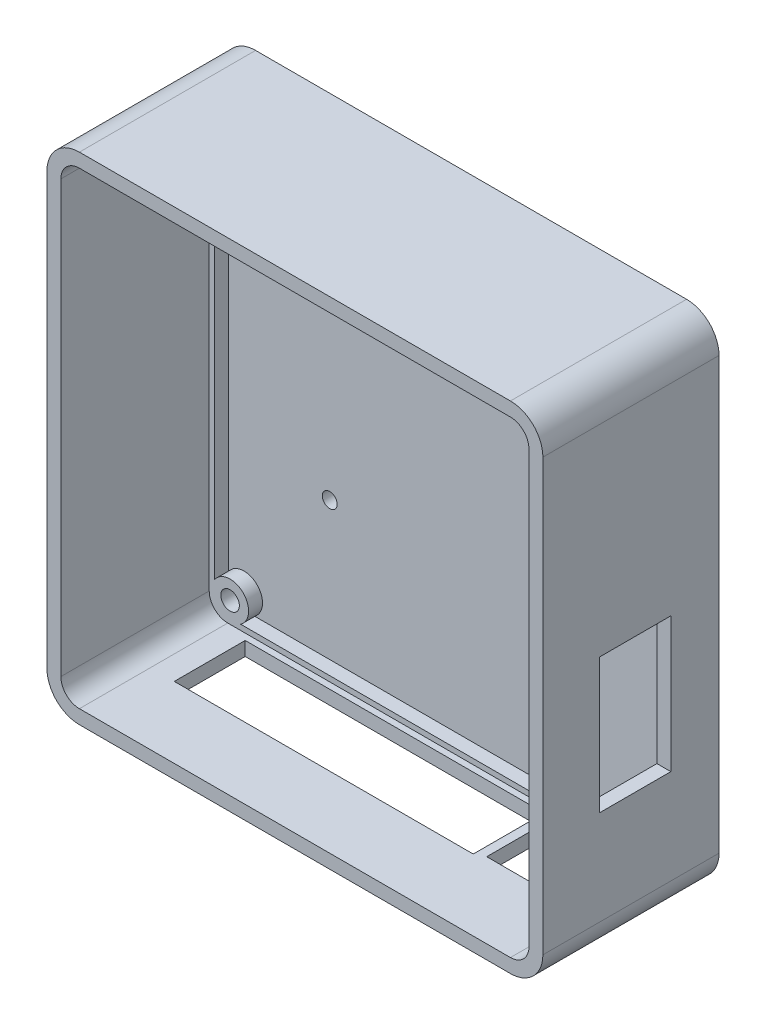
SolidWorks part; units mm, degrees
ref_plane "Piano frontale" through (0, 0, 0) normal (0, 0, 1) x (1, 0, 0)
ref_plane "Piano superiore" through (0, 0, 0) normal (0, 1, 0) x (1, 0, 0)
ref_plane "Piano destro" through (0, 0, 0) normal (1, 0, 0) x (0, 0, -1)
sketch "Schizzo1" plane through (0, 0, 94.0033) normal (0, 0, -1) x (-1, 0, 0)
  line L0 (-18.8461, 51.2441) -> (-18.8461, -40.7561) construction
  line L1 (-19.3461, 55.7314) -> (81.6287, 55.7314)
  line L2 (-19.3461, 55.7314) -> (-19.3461, -45.2434)
  line L3 (-19.3461, -45.2434) -> (81.6287, -45.2434)
  line L4 (81.6287, 55.7314) -> (81.6287, -45.2434)
  line L5 (81.1287, -40.7561) -> (81.1287, 51.2441) construction
  line L6 (77.1414, 55.2314) -> (-14.8588, 55.2314) construction
  line L7 (-14.8588, -44.7434) -> (77.1414, -44.7434) construction
  dimension "D1" = 0.5
  dimension "D2" = 0.5
  dimension "D3" = 0.5
  dimension "D4" = 0.5
extrude "Estrusione-Estrusione1" add sketch "Schizzo1" along normal blind 3
sketch "Schizzo3" plane through (0, 0, 94.0033) normal (0, 0, 1) x (1, 0, 0)
  line L0 (-81.6287, -45.2434) -> (-81.6287, 55.7314) construction
  line L1 (-81.6287, 55.7314) -> (19.3461, 55.7314) construction
  circle A0 centre (-77.1287, 51.2314) radius 2
  circle A1 centre (14.8713, 51.2314) radius 2
  circle A2 centre (-77.1287, -40.7686) radius 2
  circle A3 centre (14.8713, -40.7686) radius 2
  dimension "D5" = 4
  dimension "D6" = 4
  dimension "D7" = 4
  dimension "D8" = 4
  dimension "D1" = 4.5
  dimension "D2" = 4.5
  dimension "D3" = 92
  dimension "D4" = 92
extrude "Taglio-Estrusione1" cut sketch "Schizzo3" against normal blind 10
fillet "Raccordo1" radius 4 4 edges at (-81.6287, 55.7314, 92.5033) (-81.6287, -45.2434, 92.5033) (19.3461, -45.2434, 92.5033) (19.3461, 55.7314, 92.5033)
sketch "Schizzo4" plane through (0, 0, 94.0033) normal (0, 0, 1) x (1, 0, 0)
  line L7 (-74.8729, -44.0718) -> (12.6155, -44.0718)
  line L10 (18.1746, 48.9756) -> (18.1746, -38.5128)
  line L11 (-80.4571, 49.0129) -> (-80.4571, -38.5502)
  line L12 (-74.9102, 54.5598) -> (12.6529, 54.5598)
  arc A2 (-74.8729, -44.0718) -> (-80.4571, -38.5502) centre (-77.1287, -40.7686) ccw
  arc A4 (12.6529, 54.5598) -> (18.1746, 48.9756) centre (14.8713, 51.2314) ccw
  arc A5 (-80.4571, 49.0129) -> (-74.9102, 54.5598) centre (-77.1287, 51.2314) ccw
  arc A6 (18.1746, -38.5128) -> (12.6155, -44.0718) centre (14.8713, -40.7686) ccw
  dimension "D1" = 8
  dimension "D2" = 8
  dimension "D4" = 8
extrude "Taglio-Estrusione2" cut sketch "Schizzo4" against normal blind 3
sketch "Schizzo5" plane through (0, 0, 94.0033) normal (0, 0, 1) x (1, 0, 0)
  line L0 (19.3461, 51.7314) -> (19.3461, -41.2434) construction
  line L1 (-77.6287, 58.7314) -> (15.3461, 58.7314)
  line L2 (-84.6287, 51.7314) -> (-84.6287, -41.2434)
  line L3 (-77.6287, -48.2434) -> (15.3461, -48.2434)
  line L4 (22.3461, 51.7314) -> (22.3461, -41.2434)
  line L5 (-77.6287, 55.7314) -> (15.3461, 55.7314)
  line L6 (-81.6287, 51.7314) -> (-81.6287, -41.2434)
  line L7 (-77.6287, -45.2434) -> (15.3461, -45.2434)
  line L8 (19.3461, 51.7314) -> (19.3461, -41.2434)
  line L9 (-81.6287, -41.2434) -> (-81.6287, 51.7314) construction
  line L10 (15.3461, -45.2434) -> (-77.6287, -45.2434) construction
  arc A0 (-81.6287, -41.2434) -> (-77.6287, -45.2434) centre (-77.6287, -41.2434) ccw
  arc A1 (-81.6287, 51.7314) -> (-77.6287, 55.7314) centre (-77.6287, 51.7314) cw
  arc A2 (19.3461, -41.2434) -> (15.3461, -45.2434) centre (15.3461, -41.2434) cw
  arc A3 (19.3461, 51.7314) -> (15.3461, 55.7314) centre (15.3461, 51.7314) ccw
  arc A4 (-77.6287, -48.2434) -> (-84.6287, -41.2434) centre (-77.6287, -41.2434) cw
  arc A5 (22.3461, -41.2434) -> (15.3461, -48.2434) centre (15.3461, -41.2434) cw
  arc A6 (15.3461, 58.7314) -> (22.3461, 51.7314) centre (15.3461, 51.7314) cw
  arc A7 (-84.6287, 51.7314) -> (-77.6287, 58.7314) centre (-77.6287, 51.7314) cw
  dimension "D1" = 4
  dimension "D2" = 4
  dimension "D10" = 4
  dimension "D11" = 4
  dimension "D12" = 7
  dimension "D13" = 7
  dimension "D14" = 7
  dimension "D15" = 7
  dimension "D3" = 0
  dimension "D4" = 0
  dimension "D5" = 3
  dimension "D6" = 3
  dimension "D7" = 3
  dimension "D8" = 0
  dimension "D9" = 3
extrude "Estrusione-Estrusione2" add sketch "Schizzo5" along normal blind 32 and the other way blind 3
sketch "Schizzo6" plane through (0, 0, 91.0033) normal (0, 0, -1) x (-1, 0, 0)
  line L1 (-15.3461, 58.7314) -> (77.6287, 58.7314)
  line L2 (-22.3461, 51.7314) -> (-22.3461, -41.2434)
  line L3 (-15.3461, -48.2434) -> (77.6287, -48.2434)
  line L4 (84.6287, 51.7314) -> (84.6287, -41.2434)
  arc A0 (-15.3461, 58.7314) -> (-22.3461, 51.7314) centre (-15.3461, 51.7314) ccw
  arc A1 (84.6287, 51.7314) -> (77.6287, 58.7314) centre (77.6287, 51.7314) ccw
  arc A2 (84.6287, -41.2434) -> (77.6287, -48.2434) centre (77.6287, -41.2434) cw
  arc A3 (-22.3461, -41.2434) -> (-15.3461, -48.2434) centre (-15.3461, -41.2434) ccw
  dimension "D1" = 7
  dimension "D2" = 7
  dimension "D3" = 7
  dimension "D4" = 7
extrude "Estrusione-Estrusione3" add sketch "Schizzo6" along normal blind 3
sketch "Schizzo7" plane through (0, -48.2434, 0) normal (0, -1, 0) x (1, 0, 0)
  line L5 (9.6973, 109.4215) -> (-5.5457, 109.4215) construction
  line L6 (-6.0456, 109.7215) -> (10.1972, 109.7215)
  line L7 (-6.0456, 109.7215) -> (-6.0456, 95.2894)
  line L8 (-6.0456, 95.2894) -> (10.1972, 95.2894)
  line L9 (10.1972, 109.7215) -> (10.1972, 95.2894)
  line L10 (-5.7456, 109.2216) -> (-5.7456, 95.7878) construction
  line L11 (9.8972, 95.7878) -> (9.8972, 109.2216) construction
  line L12 (14.8588, 95.5894) -> (-77.1414, 95.5894) construction
  line L14 (-7.9973, 110.6773) -> (-72.4933, 110.6773)
  line L15 (-7.9973, 110.6773) -> (-7.9973, 95.3773)
  line L16 (-7.9973, 95.3773) -> (-72.4933, 95.3773)
  line L17 (-72.4933, 110.6773) -> (-72.4933, 95.3773)
  line L20 (-69.5806, 99.9166) -> (-69.5806, 99.2379) construction
  line L21 (-8.4973, 96.7587) -> (-8.4973, 102.7201) construction
  line L22 (-71.9933, 102.8894) -> (-71.9933, 96.5894) construction
  point P25 (-69.5806, 99.5773)
  dimension "D1" = 0.3
  dimension "D2" = 0.3
  dimension "D3" = 0.3
  dimension "D4" = 0.3
  dimension "D5" = 15.3
  dimension "D6" = 4.2
  dimension "D7" = 0.5
  dimension "D8" = 0.5
extrude "Taglio-Estrusione3" cut sketch "Schizzo7" against normal up to next
sketch "Schizzo8" plane through (22.3461, 0, 0) normal (1, 0, 0) x (0, 0, -1)
  line L1 (-113.8016, 8.2883) -> (-98.4016, 8.2883)
  line L2 (-113.8016, 8.2883) -> (-113.8016, -20.8171)
  line L3 (-113.8016, -20.8171) -> (-98.4016, -20.8171)
  line L4 (-98.4016, 8.2883) -> (-98.4016, -20.8171)
  line L8 (-109.9409, 4.6211) -> (-109.2622, 4.6211) construction
  line L9 (-106.2894, 7.7883) -> (-112.5894, 7.7883) construction
  line L10 (-112.5894, -20.3171) -> (-106.2894, -20.3171) construction
  point P12 (-109.6016, 4.6211)
  dimension "D1" = 4.2
  dimension "D2" = 0.5
  dimension "D3" = 0.5
  dimension "D4" = 15.4
extrude "Taglio-Estrusione4" cut sketch "Schizzo8" against normal up to next
chamfer "Smusso1" distance 3 angle 45 1 edges at (2.0758, -48.2434, 95.2894)
sketch "Schizzo9" plane through (0, 0, 94.0033) normal (0, 0, 1) x (1, 0, 0)
  circle A0 centre (-77.1287, 51.2314) radius 2
  circle A1 centre (14.8713, 51.2314) radius 1.8555
  circle A2 centre (14.8713, -40.7686) radius 2
  circle A3 centre (-77.1287, -40.7686) radius 2
extrude "Taglio-Estrusione5" cut sketch "Schizzo9" against normal through all
sketch "Schizzo10" plane through (0, 0, 88.0033) normal (0, 0, -1) x (-1, 0, 0)
  circle A0 centre (3.6539, 31.7314) radius 1.6
  circle A1 centre (3.6539, -14.2686) radius 1.6
  circle A2 centre (58.6287, -14.2686) radius 1.6
  circle A3 centre (58.6287, 31.7314) radius 1.6
extrude "Taglio-Estrusione6" cut sketch "Schizzo10" against normal blind 5
